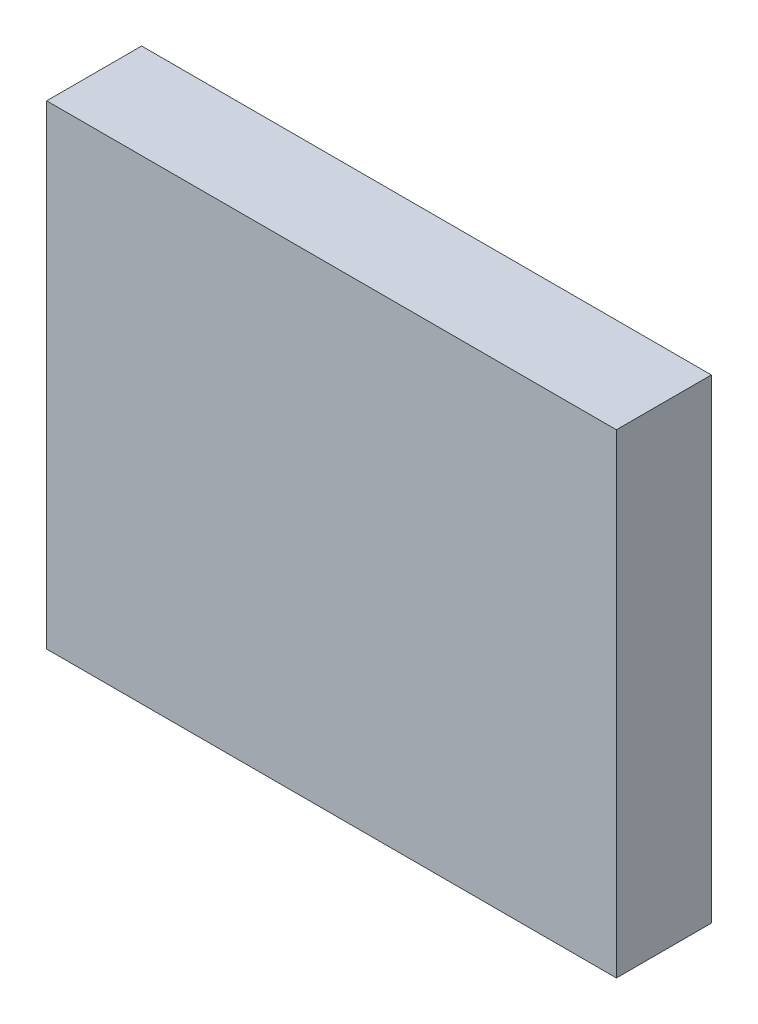
SolidWorks part; units mm, degrees
ref_plane "前视基准面" through (0, 0, 0) normal (0, 0, 1) x (1, 0, 0)
ref_plane "上视基准面" through (0, 0, 0) normal (0, 1, 0) x (1, 0, 0)
ref_plane "右视基准面" through (0, 0, 0) normal (1, 0, 0) x (0, 0, -1)
sketch "草图1" plane through (0, 0, 0) normal (0, 0, 1) x (1, 0, 0)
  line L0 (-30, -30) -> (30, -30) construction
  line L1 (-60, 50) -> (60, 50)
  line L2 (-60, 50) -> (-60, -50)
  line L3 (-60, -50) -> (60, -50)
  line L4 (60, 50) -> (60, -50)
  line L5 (-60, 50) -> (60, -50) construction
  line L6 (-60, -50) -> (60, 50) construction
  line L7 (-30, -22) -> (30, -22)
  line L8 (-30, -38) -> (30, -38)
  line L9 (0, 66.4251) -> (0, -66.2641) construction
  circle A0 centre (0, 0) radius 12.5
  arc A1 (-30, -22) -> (-30, -38) centre (-30, -30) ccw
  arc A2 (30, -38) -> (30, -22) centre (30, -30) ccw
  point P0 (0, 0)
  point P10 (0, -30)
  dimension "D3" = 25
  dimension "D4" = 8
  dimension "D1" = 100
  dimension "D2" = 120
  dimension "D5" = 60
  dimension "D6" = 30
extrude "凸台-拉伸1" add sketch "草图1" along normal blind 20 contours L1 L4 L3 L2
extrude "切除-拉伸2" cut sketch "草图1<3>" along normal blind 10 contours A0 | L7 A2 L8 A1
sketch "草图1<3>" plane through (0, 0, 0) normal (0, 0, 1) x (1, 0, 0) same geometry as "草图1"
